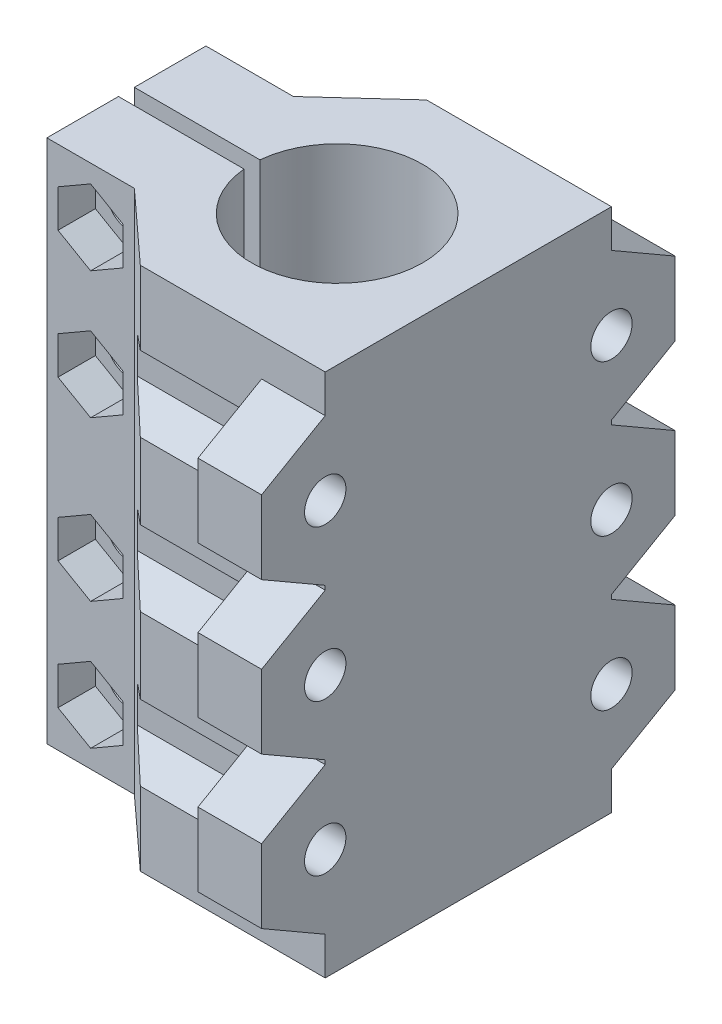
SolidWorks part; units mm, degrees
ref_plane "Спереди" through (0, 0, 0) normal (0, 0, 1) x (1, 0, 0)
ref_plane "Сверху" through (0, 0, 0) normal (0, 1, 0) x (1, 0, 0)
ref_plane "Справа" through (0, 0, 0) normal (1, 0, 0) x (0, 0, -1)
sketch "Эскиз1" plane through (0, 0, 0) normal (0, 1, 0) x (1, 0, 0)
  line L0 (-21.5, 10) -> (-21.5, 1)
  line L1 (-1.7509, 18) -> (13.5, 18)
  line L2 (-21.5, 0) -> (38.8776, 0) construction
  line L3 (-1.7509, -18) -> (13.5, -18)
  line L4 (21.5, 18) -> (21.5, -18)
  line L5 (-21.5, -1) -> (-21.5, -10)
  line L6 (-21.5, 1) -> (-5.4523, 1)
  line L7 (-1.7509, 18) -> (-1.7509, -18) construction
  line L8 (-21.5, -1) -> (-5.4523, -1)
  line L9 (-21.5, 10) -> (-10.5, 10)
  line L10 (-10.5, 10) -> (-1.7509, 18)
  line L11 (-10.5, -10) -> (-1.7509, -18)
  line L12 (-21.5, -10) -> (-10.5, -10)
  line L13 (21.5, -18) -> (21.5, -26)
  line L14 (21.5, -26) -> (13.5, -26)
  line L15 (13.5, -26) -> (13.5, -18)
  line L16 (21.5, 18) -> (21.5, 26)
  line L17 (21.5, 26) -> (13.5, 26)
  line L18 (13.5, 26) -> (13.5, 18)
  arc A0 (-5.4523, -1) -> (-5.4523, 1) centre (5, 0) ccw
  point P0 (0, 0)
  point P5 (-1.7509, 18)
  point P9 (21.5, 0)
  point P12 (15.5, 0)
  point P13 (-1.7509, -18)
  dimension "D4" = 21
  dimension "D1" = 8
  dimension "D2" = 36
  dimension "D3" = 6
  dimension "D5" = 8
extrude "Бобышка-Вытянуть5" add sketch "Эскиз1" along normal blind 66 contours A0 L6 L0 L9 L10 L1 L18 L17 L16 L4 L13 L14 L15 L3 L11 L12 L5 L8
sketch "Эскиз6" plane through (21.5, 0, 0) normal (1, 0, 0) x (0, 0, -1)
  line L1 (-26, 66) -> (26, 66) construction
  line L2 (0, 77.6337) -> (0, -17.4765) construction
  line L3 (26, 0) -> (-26, 0) construction
  line L5 (-18, 66) -> (-18, 61.2376)
  line L6 (-26, 66) -> (-26, 0) construction
  line L7 (-18, 42.7624) -> (-10, 47.3812)
  line L8 (-10, 47.3812) -> (-10, 56.6188)
  line L9 (-10, 56.6188) -> (-18, 61.2376)
  line L10 (-18, 61.2376) -> (-26, 56.6188)
  line L11 (-26, 56.6188) -> (-26, 47.3812)
  line L12 (-26, 47.3812) -> (-18, 42.7624)
  line L13 (-18, 23.7624) -> (-10, 28.3812)
  line L14 (-10, 28.3812) -> (-10, 37.6188)
  line L15 (-10, 37.6188) -> (-18, 42.2376)
  line L16 (-18, 42.2376) -> (-26, 37.6188)
  line L17 (-26, 37.6188) -> (-26, 28.3812)
  line L18 (-26, 28.3812) -> (-18, 23.7624)
  line L19 (-18, 4.7624) -> (-10, 9.3812)
  line L20 (-10, 9.3812) -> (-10, 18.6188)
  line L21 (-10, 18.6188) -> (-18, 23.2376)
  line L22 (-18, 23.2376) -> (-26, 18.6188)
  line L23 (-26, 18.6188) -> (-26, 9.3812)
  line L24 (-26, 9.3812) -> (-18, 4.7624)
  line L25 (-26, 0) -> (-26, 0.0836)
  line L26 (-18, 0) -> (-18, 4.7624)
  line L27 (26, 9.3812) -> (18, 4.7624)
  line L28 (26, 18.6188) -> (26, 9.3812)
  line L29 (18, 23.2376) -> (26, 18.6188)
  line L30 (10, 18.6188) -> (18, 23.2376)
  line L31 (10, 9.3812) -> (10, 18.6188)
  line L32 (18, 4.7624) -> (10, 9.3812)
  line L33 (26, 28.3812) -> (18, 23.7624)
  line L34 (26, 37.6188) -> (26, 28.3812)
  line L35 (18, 42.2376) -> (26, 37.6188)
  line L36 (10, 37.6188) -> (18, 42.2376)
  line L37 (10, 28.3812) -> (10, 37.6188)
  line L38 (18, 23.7624) -> (10, 28.3812)
  line L39 (26, 47.3812) -> (18, 42.7624)
  line L40 (26, 56.6188) -> (26, 47.3812)
  line L41 (18, 61.2376) -> (26, 56.6188)
  line L42 (10, 56.6188) -> (18, 61.2376)
  line L43 (10, 47.3812) -> (10, 56.6188)
  line L44 (18, 42.7624) -> (10, 47.3812)
  line L45 (18, 61.2376) -> (18, 66)
  line L46 (18, 4.7624) -> (18, 0)
  line L47 (18, 23.2376) -> (18, 23.7624)
  line L48 (18, 42.2376) -> (18, 42.7624)
  line L49 (-18, 42.2376) -> (-18, 42.7624)
  line L50 (-18, 23.2376) -> (-18, 23.7624)
  circle A0 centre (-18, 52) radius 8 construction
  circle A1 centre (-18, 33) radius 8 construction
  circle A2 centre (-18, 14) radius 8 construction
  circle A3 centre (18, 14) radius 8 construction
  circle A4 centre (18, 33) radius 8 construction
  circle A5 centre (18, 52) radius 8 construction
  circle A6 centre (-18, 52) radius 2.5
  circle A7 centre (-18, 33) radius 2.5
  circle A8 centre (-18, 14) radius 2.5
  circle A9 centre (18, 14) radius 2.5
  circle A10 centre (18, 33) radius 2.5
  circle A11 centre (18, 52) radius 2.5
  line M34 (-26, 0) -> (26, 0)
  line M35 (26, 0) -> (26, 66)
  line M36 (26, 66) -> (-26, 66)
  line M37 (-26, 66) -> (-26, 0)
  dimension "D2" = 3
  dimension "D1" = 5
  dimension "D3" = 4.7624
extrude "Вырез-Вытянуть1" cut sketch "Эскиз6" against normal through all contours L10 L5 M36 M37 | L16 L49 L12 M37 | L22 L50 L18 M37 | L26 L24 M34 M37 | L27 L46 M34 M35 | L47 L29 L33 M35 | L48 L35 L39 M35 | L45 L41 M35 M36 region at (21.5, 62.3384, 22.4354) region at (21.5, 62.3384, -22.4354) region at (21.5, 42.5, 23.1973) region at (21.5, 42.5, -23.1973) region at (21.5, 23.5, 23.1973) region at (21.5, 23.5, -23.1973) region at (21.5, 3.6616, 22.4354) region at (21.5, 3.6616, -22.4354)
sketch "Эскиз7" plane through (21.5, 0, 0) normal (1, 0, 0) x (0, 0, -1)
extrude "Вырез-Вытянуть3" cut sketch "Эскиз6<4>" against normal through all contours A6 | A7 | A8 | A9 | A10 | A11 region at (21.5, 52, 18) region at (21.5, 33, 18) region at (21.5, 14, 18) region at (21.5, 14, -18) region at (21.5, 33, -18) region at (21.5, 52, -18)
sketch "Эскиз6<4>" plane through (21.5, 0, 0) normal (1, 0, 0) x (0, 0, -1) same geometry as "Эскиз6"
sketch "Эскиз10" plane through (21.5, 0, 0) normal (1, 0, 0) x (0, 0, -1)
  line L0 (26, 18.6188) -> (26, 9.3812) construction
  line L1 (14, 16.3094) -> (14, 11.6906)
  line L2 (14, 11.6906) -> (18, 9.3812)
  line L3 (18, 9.3812) -> (22, 11.6906)
  line L4 (22, 11.6906) -> (22, 16.3094)
  line L5 (22, 16.3094) -> (18, 18.6188)
  line L6 (18, 18.6188) -> (14, 16.3094)
  line L7 (14, 35.3094) -> (14, 30.6906)
  line L8 (14, 30.6906) -> (18, 28.3812)
  line L9 (18, 28.3812) -> (22, 30.6906)
  line L10 (22, 30.6906) -> (22, 35.3094)
  line L11 (22, 35.3094) -> (18, 37.6188)
  line L12 (18, 37.6188) -> (14, 35.3094)
  line L13 (14, 54.3094) -> (14, 49.6906)
  line L14 (14, 49.6906) -> (18, 47.3812)
  line L15 (18, 47.3812) -> (22, 49.6906)
  line L16 (22, 49.6906) -> (22, 54.3094)
  line L17 (22, 54.3094) -> (18, 56.6188)
  line L18 (18, 56.6188) -> (14, 54.3094)
  line L19 (0, -12.5833) -> (0, 76.6202) construction
  line L20 (-18, 56.6188) -> (-14, 54.3094)
  line L21 (-22, 54.3094) -> (-18, 56.6188)
  line L22 (-22, 49.6906) -> (-22, 54.3094)
  line L23 (-18, 47.3812) -> (-22, 49.6906)
  line L24 (-14, 49.6906) -> (-18, 47.3812)
  line L25 (-14, 54.3094) -> (-14, 49.6906)
  line L26 (-18, 37.6188) -> (-14, 35.3094)
  line L27 (-22, 35.3094) -> (-18, 37.6188)
  line L28 (-22, 30.6906) -> (-22, 35.3094)
  line L29 (-18, 28.3812) -> (-22, 30.6906)
  line L30 (-14, 30.6906) -> (-18, 28.3812)
  line L31 (-14, 35.3094) -> (-14, 30.6906)
  line L32 (-18, 18.6188) -> (-14, 16.3094)
  line L33 (-22, 16.3094) -> (-18, 18.6188)
  line L34 (-22, 11.6906) -> (-22, 16.3094)
  line L35 (-18, 9.3812) -> (-22, 11.6906)
  line L36 (-14, 11.6906) -> (-18, 9.3812)
  line L37 (-14, 16.3094) -> (-14, 11.6906)
  circle A0 centre (18, 14) radius 4 construction
  circle A1 centre (18, 33) radius 4 construction
  circle A2 centre (18, 52) radius 4 construction
  circle A3 centre (-18, 52) radius 4 construction
  circle A4 centre (-18, 33) radius 4 construction
  circle A5 centre (-18, 14) radius 4 construction
  dimension "D2" = 3
  dimension "D1" = 8
extrude "Вырез-Вытянуть5" cut sketch "Эскиз10" against normal through all
sketch "Эскиз12" plane through (21.5, 0, 0) normal (1, 0, 0) x (0, 0, -1)
  line L0 (-18, 56.6188) -> (-18, 9.3812) construction
  line L1 (18, 56.6188) -> (18, 9.3812) construction
  line L2 (-22, 54.3094) -> (-14, 49.6906) construction
  line L3 (-14, 49.6906) -> (-14, 54.3094) construction
  line L4 (-14, 54.3094) -> (-22, 49.6906) construction
  line L5 (-22, 35.3094) -> (-14, 30.6906) construction
  line L6 (-14, 30.6906) -> (-14, 35.3094) construction
  line L7 (-14, 35.3094) -> (-22, 30.6906) construction
  line L8 (-22, 16.3094) -> (-14, 11.6906) construction
  line L9 (-14, 11.6906) -> (-14, 16.3094) construction
  line L10 (-14, 16.3094) -> (-22, 11.6906) construction
  line L11 (14, 54.3094) -> (22, 49.6906) construction
  line L12 (22, 49.6906) -> (22, 54.3094) construction
  line L13 (22, 54.3094) -> (14, 49.6906) construction
  line L14 (14, 35.3094) -> (22, 30.6906) construction
  line L15 (22, 30.6906) -> (22, 35.3094) construction
  line L16 (22, 35.3094) -> (14, 30.6906) construction
  line L17 (14, 16.3094) -> (22, 11.6906) construction
  line L18 (22, 11.6906) -> (22, 16.3094) construction
  line L19 (22, 16.3094) -> (14, 11.6906) construction
  line L21 (-14, 49.6906) -> (-14, 54.3094)
  line L22 (-14, 54.3094) -> (-18, 56.6188)
  line L23 (-18, 56.6188) -> (-22, 54.3094)
  line L24 (-22, 54.3094) -> (-22, 49.6906)
  line L25 (-22, 49.6906) -> (-18, 47.3812)
  line L26 (-18, 47.3812) -> (-14, 49.6906)
  line L27 (-14, 30.6906) -> (-14, 35.3094)
  line L28 (-14, 35.3094) -> (-18, 37.6188)
  line L29 (-18, 37.6188) -> (-22, 35.3094)
  line L30 (-22, 35.3094) -> (-22, 30.6906)
  line L31 (-22, 30.6906) -> (-18, 28.3812)
  line L32 (-18, 28.3812) -> (-14, 30.6906)
  line L33 (-14, 11.6906) -> (-14, 16.3094)
  line L34 (-14, 16.3094) -> (-18, 18.6188)
  line L35 (-18, 18.6188) -> (-22, 16.3094)
  line L36 (-22, 16.3094) -> (-22, 11.6906)
  line L37 (-22, 11.6906) -> (-18, 9.3812)
  line L38 (-18, 9.3812) -> (-14, 11.6906)
  line L39 (22, 49.6906) -> (22, 54.3094)
  line L40 (22, 54.3094) -> (18, 56.6188)
  line L41 (18, 56.6188) -> (14, 54.3094)
  line L42 (14, 54.3094) -> (14, 49.6906)
  line L43 (14, 49.6906) -> (18, 47.3812)
  line L44 (18, 47.3812) -> (22, 49.6906)
  line L45 (22, 30.6906) -> (22, 35.3094)
  line L46 (22, 35.3094) -> (18, 37.6188)
  line L47 (18, 37.6188) -> (14, 35.3094)
  line L48 (14, 35.3094) -> (14, 30.6906)
  line L49 (14, 30.6906) -> (18, 28.3812)
  line L50 (18, 28.3812) -> (22, 30.6906)
  line L51 (22, 11.6906) -> (22, 16.3094)
  line L52 (22, 16.3094) -> (18, 18.6188)
  line L53 (18, 18.6188) -> (14, 16.3094)
  line L54 (14, 16.3094) -> (14, 11.6906)
  line L55 (14, 11.6906) -> (18, 9.3812)
  line L56 (18, 9.3812) -> (22, 11.6906)
  circle A0 centre (-18, 52) radius 4 construction
  circle A1 centre (-18, 33) radius 4 construction
  circle A2 centre (-18, 14) radius 4 construction
  circle A3 centre (18, 52) radius 4 construction
  circle A4 centre (18, 33) radius 4 construction
  circle A5 centre (18, 14) radius 4 construction
  circle A6 centre (-18, 52) radius 2.5
  circle A7 centre (-18, 33) radius 2.5
  circle A8 centre (-18, 14) radius 2.5
  circle A9 centre (18, 52) radius 2.5
  circle A10 centre (18, 33) radius 2.5
  circle A11 centre (18, 14) radius 2.5
extrude "Бобышка-Вытянуть9" add sketch "Эскиз12" against normal blind 4 contours L56 L51 L52 L53 L54 L55 | L38 L33 L34 L35 L36 L37 | L32 L27 L28 L29 L30 L31 | L26 L21 L22 L23 L24 L25 | L44 L39 L40 L41 L42 L43 | L50 L45 L46 L47 L48 L49
sketch "Эскиз16" plane through (17.5, 0, 0) normal (-1, 0, 0) x (0, 0, 1)
  line L0 (-22, 54.3094) -> (-14, 49.6906) construction
  line L1 (-14, 49.6906) -> (-14, 54.3094) construction
  line L2 (-14, 54.3094) -> (-22, 49.6906) construction
  line L3 (-18, 56.6188) -> (-18, 9.3812) construction
  line L4 (18, 56.6188) -> (18, 9.3812) construction
  line L5 (-22, 30.6906) -> (-14, 35.3094) construction
  line L6 (-14, 35.3094) -> (-14, 30.6906) construction
  line L7 (-14, 30.6906) -> (-22, 35.3094) construction
  line L8 (-22, 11.6906) -> (-14, 16.3094) construction
  line L9 (-14, 16.3094) -> (-14, 11.6906) construction
  line L10 (-14, 11.6906) -> (-22, 16.3094) construction
  line L11 (14, 11.6906) -> (22, 16.3094) construction
  line L12 (22, 16.3094) -> (22, 11.6906) construction
  line L13 (22, 11.6906) -> (14, 16.3094) construction
  line L14 (14, 30.6906) -> (22, 35.3094) construction
  line L15 (22, 35.3094) -> (22, 30.6906) construction
  line L16 (22, 30.6906) -> (14, 35.3094) construction
  line L17 (14, 49.6906) -> (22, 54.3094) construction
  line L18 (22, 54.3094) -> (22, 49.6906) construction
  line L19 (22, 49.6906) -> (14, 54.3094) construction
  circle A0 centre (-18, 52) radius 2.5
  circle A1 centre (-18, 33) radius 2.5
  circle A2 centre (-18, 14) radius 2.5
  circle A3 centre (18, 14) radius 2.5
  circle A4 centre (18, 33) radius 2.5
  circle A5 centre (18, 52) radius 2.5
extrude "Вырез-Вытянуть6" cut sketch "Эскиз16" against normal through all
sketch "Эскиз21" plane through (0, 0, 10) normal (0, 0, 1) x (1, 0, 0)
  line L0 (-16, 66) -> (-16, 0) construction
  line L1 (-21.5, 66) -> (-10.5, 66) construction
  line L2 (-21.5, 0) -> (-10.5, 0) construction
  line L3 (-16, 66) -> (-16, 59)
  line L4 (-21.5, 33) -> (31.462, 33) construction
  line L5 (-21.5, 66) -> (-21.5, 0) construction
  circle A0 centre (-16, 59) radius 2.5
  circle A1 centre (-16, 43) radius 2.5
  circle A2 centre (-16, 23) radius 2.5
  circle A3 centre (-16, 7) radius 2.5
  circle A4 centre (-16, 33) radius 2.5
  dimension "D2" = 2
  dimension "D1" = 7
extrude "Вырез-Вытянуть9" cut sketch "Эскиз21" against normal through all contours A0 | A1 | A4 | A2 | A3 region at (-17.7178, 57.2822, 10) region at (-16, 43, 10) region at (-16, 23, 10) region at (-16, 7, 10) region at (-16, 33, 10)
sketch "Эскиз22" plane through (0, 0, 10) normal (0, 0, 1) x (1, 0, 0)
  line L0 (-21.5, 66) -> (-21.5, 0) construction
  line L1 (-12, 56.6906) -> (-12, 61.3094)
  line L2 (-12, 61.3094) -> (-16, 63.6188)
  line L3 (-16, 63.6188) -> (-20, 61.3094)
  line L4 (-20, 61.3094) -> (-20, 56.6906)
  line L5 (-20, 56.6906) -> (-16, 54.3812)
  line L6 (-16, 54.3812) -> (-12, 56.6906)
  line L7 (-12, 40.6906) -> (-12, 45.3094)
  line L8 (-12, 45.3094) -> (-16, 47.6188)
  line L9 (-16, 47.6188) -> (-20, 45.3094)
  line L10 (-20, 45.3094) -> (-20, 40.6906)
  line L11 (-20, 40.6906) -> (-16, 38.3812)
  line L12 (-16, 38.3812) -> (-12, 40.6906)
  line L13 (-21.5, 33) -> (25.815, 33) construction
  line L14 (-16, 27.6188) -> (-12, 25.3094)
  line L15 (-20, 25.3094) -> (-16, 27.6188)
  line L16 (-20, 20.6906) -> (-20, 25.3094)
  line L17 (-16, 18.3812) -> (-20, 20.6906)
  line L18 (-12, 20.6906) -> (-16, 18.3812)
  line L19 (-12, 25.3094) -> (-12, 20.6906)
  line L20 (-16, 11.6188) -> (-12, 9.3094)
  line L21 (-20, 9.3094) -> (-16, 11.6188)
  line L22 (-20, 4.6906) -> (-20, 9.3094)
  line L23 (-16, 2.3812) -> (-20, 4.6906)
  line L24 (-12, 4.6906) -> (-16, 2.3812)
  line L25 (-12, 9.3094) -> (-12, 4.6906)
  circle A0 centre (-16, 59) radius 4 construction
  circle A1 centre (-16, 43) radius 4 construction
  circle A2 centre (-16, 23) radius 4 construction
  circle A3 centre (-16, 7) radius 4 construction
  dimension "D1" = 8
  dimension "D2" = 2
extrude "Вырез-Вытянуть10" cut sketch "Эскиз22" against normal blind 4.7
sketch "Эскиз25" plane through (-21.5, 0, 0) normal (-1, 0, 0) x (0, 0, 1)
  line L0 (-10, 66) -> (-10, 0) construction
  line L2 (-10, 0) -> (-10, 15)
  line L3 (-10, 15) -> (-10, 33)
  line L5 (-10, 15) -> (-5.5, 15)
  line L6 (-10, 33) -> (-5.5, 33)
  circle A0 centre (-5.5, 15) radius 1.5
  circle A1 centre (-5.5, 33) radius 1.5
  dimension "D3" = 3
  dimension "D4" = 3
  dimension "D1" = 15
  dimension "D2" = 4.5
sketch "Эскиз26" plane through (0, 0, -10) normal (0, 0, -1) x (-1, 0, 0)
  circle A0 centre (16, 33) radius 2.5
extrude "Бобышка-Вытянуть11" add sketch "Эскиз26" against normal blind 9
sketch "Эскиз27" plane through (0, 0, 10) normal (0, 0, 1) x (1, 0, 0)
  circle A0 centre (-16, 33) radius 2.5
extrude "Бобышка-Вытянуть12" add sketch "Эскиз27" against normal blind 9
extrude "Вырез-Вытянуть12" cut sketch "Эскиз25" against normal blind 10 contours A1 | A0
sketch "Эскиз30" plane through (0, 0, -10) normal (0, 0, -1) x (-1, 0, 0)
  line L0 (16, 0) -> (16, 15)
  line L1 (21.5, 0) -> (10.5, 0) construction
  line L2 (17.25, 35.75) -> (17.25, 30.25)
  line L3 (14.75, 17.75) -> (17.25, 17.75)
  line L4 (14.75, 17.75) -> (14.75, 12.25)
  line L5 (14.75, 12.25) -> (17.25, 12.25)
  line L6 (16, 11.6335) -> (16, 15)
  line L7 (17.25, 17.75) -> (17.25, 12.25)
  line L9 (14.75, 17.75) -> (17.25, 12.25) construction
  line L10 (14.75, 12.25) -> (17.25, 17.75) construction
  line L11 (14.75, 30.25) -> (17.25, 30.25)
  line L12 (14.75, 35.75) -> (14.75, 30.25)
  line L13 (14.75, 35.75) -> (17.25, 35.75)
  dimension "D1" = 15
  dimension "D2" = 2.5
  dimension "D3" = 5.5
  dimension "D4" = 2
extrude "Вырез-Вытянуть13" cut sketch "Эскиз30" against normal blind 8 contours L13 L12 L11 L2 | L7 L5 L4 L3 region at (-16, 33, -10)
sketch "Эскиз31" plane through (21.5, 0, 0) normal (1, 0, 0) x (0, 0, -1)
  circle A0 centre (18, 52) radius 2.6
  circle A1 centre (18, 33) radius 2.6
  circle A2 centre (18, 14) radius 2.6
  circle A3 centre (-18, 14) radius 2.6
  circle A4 centre (-18, 33) radius 2.6
  circle A5 centre (-18, 52) radius 2.6
  dimension "D1" = 5.2
extrude "Вырез-Вытянуть14" cut sketch "Эскиз31" against normal through all
sketch "Эскиз32" plane through (-21.5, 0, 0) normal (-1, 0, 0) x (0, 0, 1)
  line L1 (18, 28.2657) -> (22.1, 30.6329)
  line L2 (22.1, 30.6329) -> (22.1, 35.3671)
  line L3 (22.1, 35.3671) -> (18, 37.7343)
  line L4 (18, 37.7343) -> (13.9, 35.3671)
  line L5 (13.9, 35.3671) -> (13.9, 30.6329)
  line L6 (13.9, 30.6329) -> (18, 28.2657)
  line L7 (18, 9.2657) -> (22.1, 11.6329)
  line L8 (22.1, 11.6329) -> (22.1, 16.3671)
  line L9 (22.1, 16.3671) -> (18, 18.7343)
  line L10 (18, 18.7343) -> (13.9, 16.3671)
  line L11 (13.9, 16.3671) -> (13.9, 11.6329)
  line L12 (13.9, 11.6329) -> (18, 9.2657)
  line L13 (-18, 9.2657) -> (-13.9, 11.6329)
  line L14 (-13.9, 11.6329) -> (-13.9, 16.3671)
  line L15 (-13.9, 16.3671) -> (-18, 18.7343)
  line L16 (-18, 18.7343) -> (-22.1, 16.3671)
  line L17 (-22.1, 16.3671) -> (-22.1, 11.6329)
  line L18 (-22.1, 11.6329) -> (-18, 9.2657)
  line L19 (-18, 28.2657) -> (-13.9, 30.6329)
  line L20 (-13.9, 30.6329) -> (-13.9, 35.3671)
  line L21 (-13.9, 35.3671) -> (-18, 37.7343)
  line L22 (-18, 37.7343) -> (-22.1, 35.3671)
  line L23 (-22.1, 35.3671) -> (-22.1, 30.6329)
  line L24 (-22.1, 30.6329) -> (-18, 28.2657)
  line L25 (-18, 47.2657) -> (-13.9, 49.6329)
  line L26 (-13.9, 49.6329) -> (-13.9, 54.3671)
  line L27 (-13.9, 54.3671) -> (-18, 56.7343)
  line L28 (-18, 56.7343) -> (-22.1, 54.3671)
  line L29 (-22.1, 54.3671) -> (-22.1, 49.6329)
  line L30 (-22.1, 49.6329) -> (-18, 47.2657)
  line L31 (18, 47.2657) -> (22.1, 49.6329)
  line L32 (22.1, 49.6329) -> (22.1, 54.3671)
  line L33 (22.1, 54.3671) -> (18, 56.7343)
  line L34 (18, 56.7343) -> (13.9, 54.3671)
  line L35 (13.9, 54.3671) -> (13.9, 49.6329)
  line L36 (13.9, 49.6329) -> (18, 47.2657)
  circle A0 centre (18, 33) radius 4.1 construction
  circle A1 centre (18, 14) radius 4.1 construction
  circle A2 centre (-18, 14) radius 4.1 construction
  circle A3 centre (-18, 33) radius 4.1 construction
  circle A4 centre (-18, 52) radius 4.1 construction
  circle A5 centre (18, 52) radius 4.1 construction
  dimension "D1" = 8.2
  dimension "D2" = 8.2
  dimension "D3" = 8.2
  dimension "D4" = 8.2
  dimension "D5" = 8.2
  dimension "D6" = 8.2
extrude "Вырез-Вытянуть15" cut sketch "Эскиз32" against normal up to vertex (39 mm away) up to point (17.5, 49.6906, -14)
sketch "Эскиз33" plane through (0, 0, 10) normal (0, 0, 1) x (1, 0, 0)
  circle A0 centre (-16, 59) radius 2.6
  circle A1 centre (-16, 43) radius 2.6
  circle A2 centre (-16, 23) radius 2.6
  circle A3 centre (-16, 7) radius 2.6
  dimension "D1" = 5.2
extrude "Вырез-Вытянуть16" cut sketch "Эскиз33" against normal through all
sketch "Эскиз34" plane through (0, 0, 10) normal (0, 0, 1) x (1, 0, 0)
  line L1 (-16, 54.2657) -> (-11.9, 56.6329)
  line L2 (-11.9, 56.6329) -> (-11.9, 61.3671)
  line L3 (-11.9, 61.3671) -> (-16, 63.7343)
  line L4 (-16, 63.7343) -> (-20.1, 61.3671)
  line L5 (-20.1, 61.3671) -> (-20.1, 56.6329)
  line L6 (-20.1, 56.6329) -> (-16, 54.2657)
  line L7 (-16, 38.2657) -> (-11.9, 40.6329)
  line L8 (-11.9, 40.6329) -> (-11.9, 45.3671)
  line L9 (-11.9, 45.3671) -> (-16, 47.7343)
  line L10 (-16, 47.7343) -> (-20.1, 45.3671)
  line L11 (-20.1, 45.3671) -> (-20.1, 40.6329)
  line L12 (-20.1, 40.6329) -> (-16, 38.2657)
  line L13 (-16, 18.2657) -> (-11.9, 20.6329)
  line L14 (-11.9, 20.6329) -> (-11.9, 25.3671)
  line L15 (-11.9, 25.3671) -> (-16, 27.7343)
  line L16 (-16, 27.7343) -> (-20.1, 25.3671)
  line L17 (-20.1, 25.3671) -> (-20.1, 20.6329)
  line L18 (-20.1, 20.6329) -> (-16, 18.2657)
  line L19 (-16, 2.2657) -> (-11.9, 4.6329)
  line L20 (-11.9, 4.6329) -> (-11.9, 9.3671)
  line L21 (-11.9, 9.3671) -> (-16, 11.7343)
  line L22 (-16, 11.7343) -> (-20.1, 9.3671)
  line L23 (-20.1, 9.3671) -> (-20.1, 4.6329)
  line L24 (-20.1, 4.6329) -> (-16, 2.2657)
  circle A0 centre (-16, 59) radius 4.1 construction
  circle A1 centre (-16, 43) radius 4.1 construction
  circle A2 centre (-16, 23) radius 4.1 construction
  circle A3 centre (-16, 7) radius 4.1 construction
  dimension "D1" = 8.2
  dimension "D2" = 8.2
  dimension "D3" = 8.2
  dimension "D4" = 8.2
extrude "Вырез-Вытянуть17" cut sketch "Эскиз34" against normal up to vertex (4.7 mm away) up to point (-20, 56.6906, 5.3)
sketch "Эскиз35" plane through (0, 0, 0) normal (0, -1, 0) x (1, 0, 0)
  circle A0 centre (5, 0) radius 10.75
  dimension "D1" = 21.5
extrude "Вырез-Вытянуть18" cut sketch "Эскиз35" against normal through all
sketch "Эскиз36" plane through (0, 0, -10) normal (0, 0, -1) x (-1, 0, 0)
  line L1 (17.25, 35.75) -> (14.75, 30.25)
  line L2 (14.75, 30.25) -> (17.25, 30.25)
  line L4 (17.75, 36.5) -> (14.25, 36.5)
  line L5 (17.75, 36.5) -> (17.75, 29.5)
  line L6 (17.75, 29.5) -> (14.25, 29.5)
  line L7 (14.75, 12.25) -> (17.25, 12.25)
  line L9 (14.25, 36.5) -> (14.25, 29.5)
  line L10 (17.75, 18.5) -> (14.25, 18.5)
  line L11 (17.75, 18.5) -> (17.75, 11.5)
  line L12 (17.75, 11.5) -> (14.25, 11.5)
  line L13 (14.25, 18.5) -> (14.25, 11.5)
  line L14 (17.75, 18.5) -> (14.25, 11.5) construction
  line L15 (17.75, 11.5) -> (14.25, 18.5) construction
  line L16 (17.75, 36.5) -> (14.25, 29.5) construction
  line L17 (17.75, 29.5) -> (14.25, 36.5) construction
  point P2 (16, 33)
  point P9 (16, 15)
  line M18 (14.75, 12.25) -> (14.75, 17.75)
  line M19 (14.75, 17.75) -> (17.25, 17.75)
  line M20 (17.25, 17.75) -> (17.25, 12.25)
  line M21 (17.25, 12.25) -> (14.75, 12.25)
  dimension "D1" = 3.5
  dimension "D2" = 7
  dimension "D3" = 7
  dimension "D4" = 3.5
extrude "Вырез-Вытянуть19" cut sketch "Эскиз36" against normal blind 7.5 contours L10 L13 L12 L11 M21 M18 M19 M20 | M18 M21 M20 M19 | L4 L9 L6 L5 region at (-16, 15, -10) region at (-17.6717, 15, -10)
sketch "Эскиз37" plane through (-21.5, 0, 0) normal (-1, 0, 0) x (0, 0, 1)
  circle A0 centre (-5.5, 33) radius 1.7
  circle A1 centre (-5.5, 15) radius 1.7
  dimension "D1" = 3.4
extrude "Вырез-Вытянуть20" cut sketch "Эскиз37" against normal blind 14
